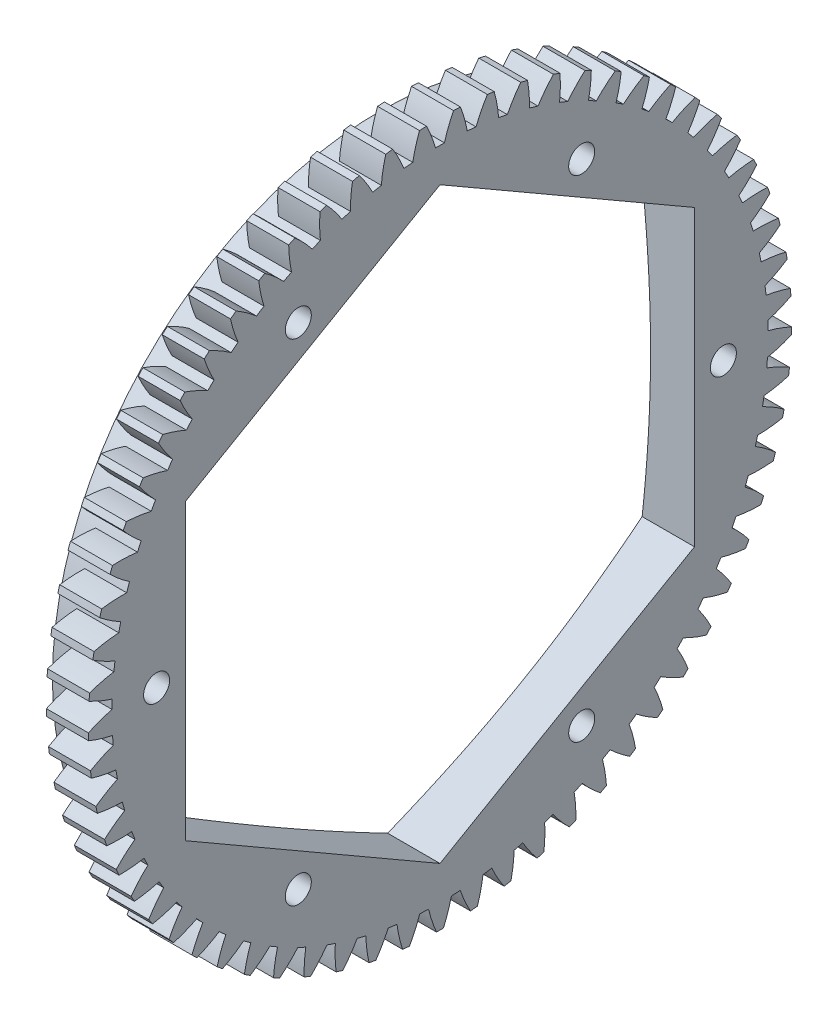
SolidWorks part; units mm, degrees
ref_plane "Plane1" through (0, 0, 0) normal (0, 0, 1) x (1, 0, 0)
ref_plane "Plane2" through (0, 0, 0) normal (0, 1, 0) x (1, 0, 0)
ref_plane "Plane3" through (0, 0, 0) normal (1, 0, 0) x (0, 0, -1)
sketch "HoldingSke" plane through (0, 0, 0) normal (0, 1, 0) x (1, 0, 0)
  line L0 (0, 0) -> (0.169, -0.3625)
  line L1 (-15, 0) -> (100, 0) construction
  line L2 (0, 0) -> (-2.1039, 2.3779)
  line L3 (0, 0) -> (-11.863, 4.5341)
  line L4 (0, 0) -> (3.6497, 7.8269)
  line L5 (0, 0) -> (-46.8476, -17.4728)
  line L6 (0, 0) -> (-9.9476, -6.7116)
  line L7 (-2.1039, 2.3779) -> (8.6586, 51.2059)
  line L8 (-76.2, 54.61) -> (-67.8, 54.61)
  line L9 (-71.009, 38.7566) -> (-53.1078, 45.2721)
  line L10 (-76.2, 71.12) -> (104.1128, 71.12)
  line L11 (0, 0) -> (-12, 0)
  line L12 (-76.2, 101.6) -> (-76.113, 101.6)
  line L13 (24.9733, 27.94) -> (52.9518, 28.4284)
  line L14 (24.9733, 27.94) -> (24.9743, 27.94)
  line L15 (24.9733, 27.94) -> (100.4006, 29.5858)
  line L16 (-63.627, -2.5) -> (-12.827, -2.5)
  circle A0 centre (0, 0) radius 70
  circle A1 centre (0, 0) radius 37.5
  circle A2 centre (0, 0) radius 37.5
  circle A3 centre (0, 0) radius 70
  dimension "MHD" = 75
  dimension "Hub_dia" = 75
  dimension "Bore" = 140
  dimension "MBD" = 140
  dimension "Num_teeth" = 65
  dimension "Pitch" = 0.4
  dimension "Overall_len" = 50
  dimension "Show_teeth" = 65
  dimension "Thickness" = 12
  dimension "OAL" = 50.0001
  dimension "T_dim" = 8.4
  dimension "Ap" = 20
  dimension "H" = 19.05
  dimension "Pitch_radius" = 180.3128
  dimension "Width" = 12
  dimension "Backlash" = 0.087
  dimension "Addendum_fac" = 1
  dimension "Dedendum_fac" = 1.25
  dimension "Clearance_fac" = 0.25
  dimension "Dedendum_add" = 0.001
  dimension "Module" = 2.5
sketch "BasProSke" plane through (0, 0, 0) normal (0, 1, 0) x (1, 0, 0)
  line L0 (-10, 0) -> (60, 0) construction
  line L1 (0, 0) -> (0, 83.75)
  line L2 (0, 0) -> (12, 0)
  line L3 (12, 0) -> (12, 83.75)
  line L4 (12, 83.75) -> (0, 83.75)
  dimension "Thickness" = 12
  dimension "Diameter" = 167.5
revolve "Base-Revolve" add sketch "BasProSke" angle 360 about L0
sketch "TooCutSke" plane through (0, 0, 0) normal (1, 0, 0) x (0, 0, -1)
  line L1 (0, 0) -> (0, 107) construction
  line L2 (0, 0) -> (-2.1155, 81.2225) construction
  line L3 (0, 0) -> (-7.849, 162.2699) construction
  line L4 (-2.1155, 81.2225) -> (-3.9245, 81.135) construction
  arc A0 (1.055, 78.1169) -> (-1.055, 78.1169) centre (0, 0) ccw
  arc A1 (3.2325, 83.713) -> (-3.2325, 83.713) centre (0, 0) ccw
  circle A2 centre (0, 0) radius 81.25 construction
  circle A3 centre (0, 0) radius 76.35 construction
  arc A4 (-1.055, 78.1169) -> (-3.2325, 83.713) centre (-32.3022, 69.1802) ccw
  arc A5 (3.2325, 83.713) -> (1.055, 78.1169) centre (32.3022, 69.1802) ccw
  dimension "Root_dia" = 156.248
  dimension "Overcut_dia" = 167.5508
  dimension "Pitch_dia" = 162.5
  dimension "Base_dia" = 152.7001
  dimension "Flank_rad" = 32.5
  dimension "Half_ang" = 2.769
  dimension "Half_CT" = 1.8111
extrude "ToothCut" cut sketch "TooCutSke" along normal through all
fillet "Breaks" [suppressed] radius 0.05 tangent propagation no
fillet "RootFillets" [suppressed] radius 0.626
pattern_circular "TeethCuts" count 65 every 5.538 about axis through (-10, 0, 0) along (1, 0, 0) of "ToothCut", "RootFillets", "Breaks"
sketch "HubNeaOneSke" plane through (0, 0, 0) normal (-1, 0, 0) x (0, 0, 1)
  circle A0 centre (0, 0) radius 37.5
  dimension "Diameter" = 75
extrude "HubNearOne" [suppressed] add sketch "HubNeaOneSke" along normal blind 38.0001
sketch "HubNeaBotSke" plane through (0, 0, 0) normal (-1, 0, 0) x (0, 0, 1)
  circle A0 centre (0, 0) radius 37.5
  dimension "Diameter" = 75
extrude "HubNearBoth" [suppressed] add sketch "HubNeaBotSke" along normal blind 19
ref_plane "FarPln" through (12, 0, 0) normal (1, 0, 0) x (0, 0, -1)
sketch "HubFarSke" plane through (12, 0, 0) normal (1, 0, 0) x (0, 0, -1)
  circle A0 centre (0, 0) radius 37.5
  dimension "Diameter" = 75
extrude "HubFar" [suppressed] add sketch "HubFarSke" along normal blind 19
sketch "BorSke" plane through (0, 0, 0) normal (1, 0, 0) x (0, 0, -1)
  circle A0 centre (0, 0) radius 70
  dimension "Diameter" = 140
extrude "Bore" cut sketch "BorSke" along normal mid plane 100.0001
sketch "KeySke" plane through (0, 0, 0) normal (1, 0, 0) x (0, 0, -1)
  line L0 (-18, 0) -> (-18, 78.4)
  line L1 (-18, 78.4) -> (18, 78.4)
  line L2 (18, 78.4) -> (18, 0)
  line L3 (0, 0) -> (0, 34) construction
  line L4 (-18, 0) -> (18, 0)
  dimension "Offset" = 78.4
  dimension "Width" = 36
extrude "Keyway" [suppressed] cut sketch "KeySke" along normal mid plane 100.0001
pattern_circular "Keyway2" [suppressed] count 2 every 90 about axis through (-10, 0, 0) along (1, 0, 0) reverse direction yes
sketch "Croquis3" plane through (0, 0, 0) normal (-1, 0, 0) x (0, 0, 1)
  line L1 (0, 70) -> (-60.6218, 35)
  line L2 (-60.6218, 35) -> (-60.6218, -35)
  line L3 (-60.6218, -35) -> (0, -70)
  line L4 (0, -70) -> (60.6218, -35)
  line L5 (60.6218, -35) -> (60.6218, 35)
  line L6 (60.6218, 35) -> (0, 70)
  circle A1 centre (0, 0) radius 70
extrude "Saliente-Extruir1" add sketch "Croquis3" against normal blind 12 contours L2 A1 | L1 A1 | L6 A1 | L5 A1 | L4 A1 | L3 A1 region at (0, 55.7681, 32.1977) region at (0, 55.7681, -32.1977) region at (0, 0, -64.3955) region at (0, 0, 64.3955) region at (0, -55.7681, -32.1977) region at (0, -55.7681, 32.1977)
sketch "Croquis4" plane through (0, 0, 0) normal (-1, 0, 0) x (0, 0, 1)
  circle A2 centre (-33.75, 58.4567) radius 3.1
  circle A3 centre (33.75, 58.4567) radius 3.1
  circle A4 centre (67.5, 0) radius 3.1
  circle A5 centre (33.75, -58.4567) radius 3.1
  circle A6 centre (-33.75, -58.4567) radius 3.1
  circle A7 centre (-67.5, 0) radius 3.1
extrude "Cortar-Extruir1" cut sketch "Croquis4" against normal blind 12
sketch "Croquis5" plane through (0, 0, 0) normal (-1, 0, 0) x (0, 0, 1)
  circle A0 centre (0, 0) radius 78.124
  circle A1 centre (0, 0) radius 60.6218
extrude "Saliente-Extruir2" add sketch "Croquis5" along normal blind 6
chamfer "Chaflán1" distance 26 angle 12 1 edges at (-6, 0, 60.6218) first distance on face at (-6, 0, 78.124)
sketch "Croquis7" plane through (0, 0, 0) normal (1, 0, 0) x (0, 0, -1)
  line L1 (-60.6218, 35) -> (-60.6218, -35)
  line L2 (-60.6218, -35) -> (0, -70)
  line L3 (0, -70) -> (60.6218, -35)
  line L4 (60.6218, -35) -> (60.6218, 35)
  line L5 (60.6218, 35) -> (0, 70)
  line L6 (0, 70) -> (-60.6218, 35)
extrude "Cortar-Extruir3" cut sketch "Croquis7" against normal blind 51
sketch "Croquis10" plane through (0, 0, 0) normal (1, 0, 0) x (0, 0, -1)
  circle A0 centre (-67.5, 0) radius 3.1
  circle A1 centre (-33.75, 58.4567) radius 3.1
  circle A2 centre (33.75, 58.4567) radius 3.1
  circle A3 centre (67.5, 0) radius 3.1
  circle A4 centre (-33.75, -58.4567) radius 3.1
  circle A5 centre (33.75, -58.4567) radius 3.1
extrude "Cortar-Extruir4" cut sketch "Croquis10" against normal blind 51
sketch "Croquis11" plane through (12, 0, 0) normal (1, 0, 0) x (0, 0, -1)
  circle A0 centre (0, 0) radius 94.9991
extrude "Cortar-Extruir5" cut sketch "Croquis11" against normal blind 2
equation "' \"Module@HoldingSke\" = 6.35"
equation "' \"Num_teeth@HoldingSke\" = 12"
equation "' \"Ap@HoldingSke\" =  20"
equation "' \"Ap@HoldingSke\" = 20"
equation "' \"Width@HoldingSke\" = 0.5 * 25.4"
equation "' \"Hub_dia@HoldingSke\"= 1 * 25.4"
equation "' \"Hub_dia@HoldingSke\" = 1 * 25.4"
equation "' \"Overall_len@HoldingSke\" = 1.0 * 25.4"
equation "' \"Bore@HoldingSke\" = 0.75 * 25.4"
equation "' \"T_dim@HoldingSke\" = 0.1 * 25.4"
equation "' \"Width@KeySke\" = 0.25 * 25.4"
equation "' \"Show_teeth@HoldingSke\" = 13"
equation "' \"Backlash@HoldingSke\" = 0.009 * 25.4"
equation "' \"Addendum_fac@HoldingSke\" = 1.0"
equation "' \"Dedendum_fac@HoldingSke\" = 1.25"
equation "' \"Dedendum_add@HoldingSke\" = 0.00005 * 25.4"
equation "' \"Clearance_fac@HoldingSke\" = 0.25"
equation "\"Pitch@HoldingSke\" = 1 / \"Module@HoldingSke\""
equation "\"Overcut_dia@TooCutSke\" = (\"Num_teeth@HoldingSke\" + 2 * \"Addendum_fac@HoldingSke\") / \"Pitch@HoldingSke\" + 0.002 * 25.4"
equation "\"Pitch_dia@TooCutSke\" = \"Num_teeth@HoldingSke\" / \"Pitch@HoldingSke\""
equation "\"Base_dia@TooCutSke\" = \"Num_teeth@HoldingSke\" / \"Pitch@HoldingSke\" * cos((\"Ap@HoldingSke\"  * 3.14159265 / 180))"
equation "\"Root_dia@TooCutSke\" = (\"Num_teeth@HoldingSke\" + 2) / \"Pitch@HoldingSke\" - 2 * (\"Addendum_fac@HoldingSke\" + \"Dedendum_fac@HoldingSke\") / \"Pitch@HoldingSke\" - \"Dedendum_add@HoldingSke\" * 2"
equation "\"Half_ang@TooCutSke\" = 180 / \"Num_teeth@HoldingSke\""
equation "\"Half_CT@TooCutSke\" = \"Num_teeth@HoldingSke\" / \"Pitch@HoldingSke\" * sin((3.14159265 / 2 / \"Num_teeth@HoldingSke\")) / 2 - 7 * \"Backlash@HoldingSke\" / 4"
equation "\"Flank_rad@TooCutSke\" = \"Num_teeth@HoldingSke\" / \"Pitch@HoldingSke\" / 5"
equation "\"Radius@RootFillets\" = \"Clearance_fac@HoldingSke\" / \"Pitch@HoldingSke\" + \"Dedendum_add@HoldingSke\""
equation "\"Break_rad@Breaks\" = 0.02 / \"Pitch@HoldingSke\""
equation "\"Thickness@HoldingSke\" = \"Width@HoldingSke\""
equation "\"OAL@HoldingSke\" = \"Thickness@HoldingSke\""
equation "\"MHD@HoldingSke\" = (\"Num_teeth@HoldingSke\" + 2) / \"Pitch@HoldingSke\" - 2 * (\"Addendum_fac@HoldingSke\" + \"Dedendum_fac@HoldingSke\")  / \"Pitch@HoldingSke\" - \"Dedendum_add@HoldingSke\" * 2"
equation "\"MBD@HoldingSke\" = (\"Num_teeth@HoldingSke\" + 2) / \"Pitch@HoldingSke\" - 2 * (\"Addendum_fac@HoldingSke\" + \"Dedendum_fac@HoldingSke\")  / \"Pitch@HoldingSke\" - \"Dedendum_add@HoldingSke\" * 2 - 0.002 * 25.4"
equation "\"MHD@HoldingSke\" = ((sgn( \"MHD@HoldingSke\" - \"Hub_dia@HoldingSke\" )-1)*( \"MHD@HoldingSke\" - \"Hub_dia@HoldingSke\" ))/-2+ \"Hub_dia@HoldingSke\""
equation "\"MBD@HoldingSke\" = ((sgn( \"MBD@HoldingSke\" - \"Bore@HoldingSke\" )-1)*( \"MBD@HoldingSke\" - \"Bore@HoldingSke\" ))/-2+ \"Bore@HoldingSke\""
equation "\"OAL@HoldingSke\" = ((sgn( \"OAL@HoldingSke\" - \"Overall_len@HoldingSke\" )+1)*( \"OAL@HoldingSke\" - \"Overall_len@HoldingSke\" ))/2 + \"Overall_len@HoldingSke\" + 0.000002 * 25.4"
equation "\"Num_teeth@TeethCuts\" = int( \"Show_teeth@HoldingSke\" ) + 1"
equation "\"Num_teeth@TeethCuts\" = ((sgn( \"Num_teeth@TeethCuts\" - \"Num_teeth@HoldingSke\" )-1)*( \"Num_teeth@TeethCuts\" - \"Num_teeth@HoldingSke\" ))/-2+ \"Num_teeth@HoldingSke\""
equation "\"Num_teeth@TeethCuts\" = ((sgn( \"Num_teeth@TeethCuts\" - 2.0)+1)*( \"Num_teeth@TeethCuts\" - 2.0))/2 +2.0"
equation "\"Angle@TeethCuts\" = 360.0 / \"Num_teeth@HoldingSke\""
equation "\"Diameter@BasProSke\" = (\"Num_teeth@HoldingSke\" + 2 * \"Addendum_fac@HoldingSke\") / \"Pitch@HoldingSke\""
equation "\"Thickness@BasProSke\"  = \"Thickness@HoldingSke\""
equation "' \"Fillet_rad@BasProSke\" =  \"Thickness@HoldingSke\" * 0.05"
equation "' \"Fillet_rad@BasProSke\" = \"Thickness@HoldingSke\" * 0.05"
equation "\"MHD@HoldingSke\" = ((sgn( \"MHD@HoldingSke\" - \"Root_dia@TooCutSke\" )-1)*( \"MHD@HoldingSke\" - \"Root_dia@TooCutSke\" ))/-2+ \"Root_dia@TooCutSke\""
equation "\"Diameter@HubNeaOneSke\" = \"MHD@HoldingSke\""
equation "\"Length@HubNearOne\" = \"OAL@HoldingSke\" - \"Thickness@BasProSke\""
equation "\"Diameter@HubNeaBotSke\" = \"MHD@HoldingSke\""
equation "\"Length@HubNearBoth\" = ( \"OAL@HoldingSke\" - \"Thickness@BasProSke\" ) / 2.0"
equation "\"Thickness@FarPln\" = \"Thickness@BasProSke\""
equation "\"Diameter@HubFarSke\" = \"MHD@HoldingSke\""
equation "\"Length@HubFar\" = ( \"OAL@HoldingSke\" - \"Thickness@BasProSke\" ) / 2.0"
equation "\"Diameter@BorSke\" = \"MBD@HoldingSke\""
equation "\"D1@Bore\" = \"OAL@HoldingSke\" * 2.0"
equation "\"D1@Keyway\" = \"OAL@HoldingSke\" * 2.0"
equation "\"Offset@KeySke\" = \"T_dim@HoldingSke\" + \"MBD@HoldingSke\" / 2.0"
